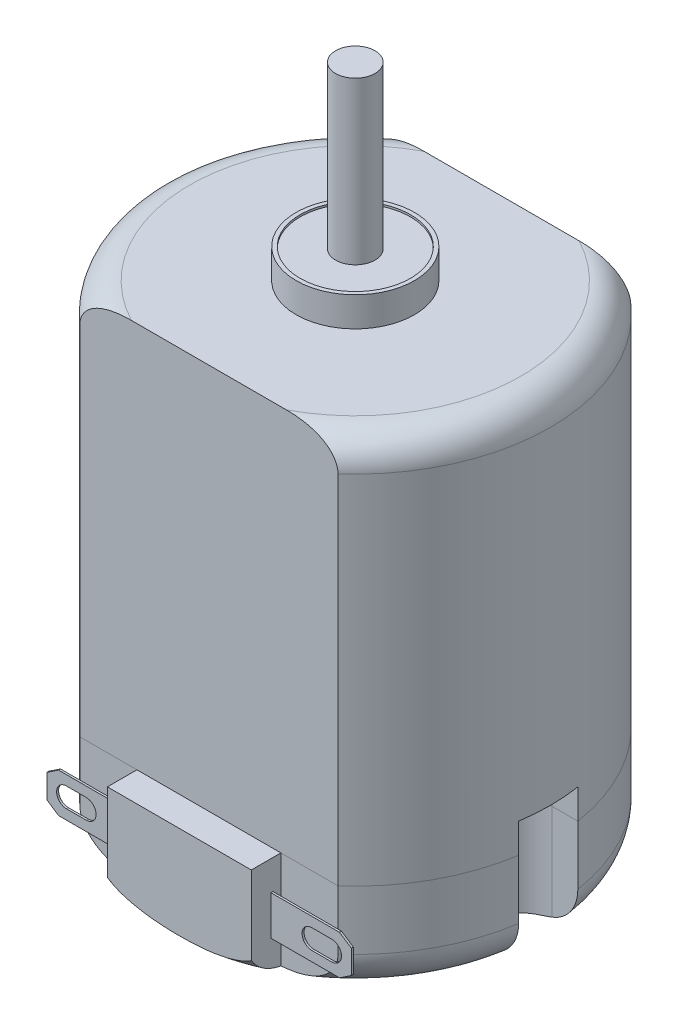
SolidWorks part; units mm, degrees
ref_plane "Front Plane" through (0, 0, 0) normal (0, 0, 1) x (1, 0, 0)
ref_plane "Top Plane" through (0, 0, 0) normal (0, 1, 0) x (1, 0, 0)
ref_plane "Right Plane" through (0, 0, 0) normal (1, 0, 0) x (0, 0, -1)
sketch "Sketch1" plane through (0, 0, 0) normal (0, 1, 0) x (1, 0, 0)
  line L0 (-6.5482, 7.425) -> (6.5482, 7.425)
  line L2 (6.5482, -7.425) -> (-6.5482, -7.425)
  arc A0 (-6.5482, 7.425) -> (-6.5482, -7.425) centre (0, 0) ccw
  arc A1 (6.5482, -7.425) -> (6.5482, 7.425) centre (0, 0) ccw
  point P1 (0, 0)
  point P4 (-6.5482, -7.425)
  dimension "D1" = 19.8
  dimension "D2" = 14.85
extrude "Boss-Extrude1" add sketch "Sketch1" along normal blind 19.6
sketch "Sketch2" plane through (0, 0, 0) normal (0, -1, 0) x (1, 0, 0)
  line L0 (6.5482, -7.425) -> (-6.5482, -7.425) construction
  line L1 (-6.5482, -7.425) -> (6.5482, -7.425)
  line L2 (-6.5482, 7.425) -> (-3.65, 7.425)
  line L3 (-6.5482, 7.425) -> (6.5482, 7.425) construction
  line L4 (-3.65, 7.425) -> (-3.65, 8.925)
  line L5 (-3.65, 8.925) -> (3.65, 8.925)
  line L6 (3.65, 8.925) -> (3.65, 7.425)
  line L7 (3.65, 7.425) -> (6.5482, 7.425)
  arc A0 (6.5482, 7.425) -> (6.5482, -7.425) centre (0, 0) cw
  arc A1 (-6.5482, 7.425) -> (-6.5482, -7.425) centre (0, 0) ccw
  arc A2 (-6.5482, 7.425) -> (-6.5482, -7.425) centre (0, 0) ccw construction
  dimension "D1" = 7.3
  dimension "D2" = 1.5
extrude "Boss-Extrude2" add sketch "Sketch2" along normal blind 5 separate body
sketch "Sketch3" plane through (0, -5, 0) normal (0, -1, 0) x (1, 0, 0)
  line L0 (-2.8652, -3.975) -> (2.8652, -3.975)
  line L1 (-6.5482, -7.425) -> (6.5482, -7.425) construction
  line L2 (0, 0) -> (0, 2.5) construction
  line L3 (-2.75, 3.4) -> (2.75, 3.4)
  line L4 (-2.75, 3.4) -> (-2.75, 2.5)
  line L5 (-2.75, 2.5) -> (2.75, 2.5)
  line L6 (2.75, 3.4) -> (2.75, 2.5)
  arc A0 (2.8652, -3.975) -> (-2.8652, -3.975) centre (0, 0) ccw
  dimension "D1" = 9.8
  dimension "D2" = 3.45
  dimension "D3" = 5.5
  dimension "D4" = 0.9
  dimension "D5" = 2.5
extrude "Boss-Extrude3" add sketch "Sketch3" along normal blind 2.3
sketch "Sketch4" plane through (0, -7.3, 0) normal (0, -1, 0) x (1, 0, 0)
  circle A0 centre (0, 0) radius 1
  dimension "D1" = 2
extrude "Boss-Extrude4" add sketch "Sketch4" along normal blind 0.5
sketch "Sketch5" plane through (0, -5, 0) normal (0, -1, 0) x (1, 0, 0)
  line L0 (-8.475, 0) -> (0, 0) construction
  line L1 (0, 0) -> (8.475, 0) construction
  line L2 (-8.475, 1.5) -> (-9.7857, 1.5)
  line L3 (8.475, 1.5) -> (9.7857, 1.5)
  line L4 (-8.475, -1.5) -> (-9.7857, -1.5)
  line L6 (8.475, -1.5) -> (9.7857, -1.5)
  arc A0 (-8.475, -1.5) -> (-8.475, 1.5) centre (-8.475, 0) ccw
  arc A1 (8.475, 1.5) -> (8.475, -1.5) centre (8.475, 0) ccw
  arc A2 (-6.5482, 7.425) -> (-6.5482, -7.425) centre (0, 0) ccw construction
  arc A3 (6.5482, -7.425) -> (6.5482, 7.425) centre (0, 0) ccw construction
  arc A4 (-9.7857, 1.5) -> (-9.7857, -1.5) centre (0, 0) ccw
  arc A5 (9.7857, -1.5) -> (9.7857, 1.5) centre (0, 0) ccw
  arc M1 (6.5482, -7.425) -> (6.5482, 7.425) centre (0, 0) ccw
  arc M7 (-6.5482, 7.425) -> (-6.5482, -7.425) centre (0, 0) ccw
  dimension "D1" = 16.95
  dimension "D2" = 1.5
extrude "Cut-Extrude1" cut sketch "Sketch5" against normal blind 6.5 contours L4 A0 L2 M7 | L3 A1 L6 M1 region at (-8.5578, -5, 0) region at (8.5578, -5, 0)
fillet "Fillet1" radius 2 3 edges at (8.6877, -5, -4.747) (-8.6877, -5, 4.747) (-8.6877, -5, -4.747)
sketch "Sketch7" plane through (0, 0, 0) normal (1, 0, 0) x (0, 0, -1)
  line L0 (-8.925, -3.9816) -> (-8.925, 0) construction
  line L1 (-7.925, -3.5) -> (-7.825, -3.5)
  line L2 (-7.925, -3.5) -> (-7.925, -1.5)
  line L3 (-7.925, -1.5) -> (-7.825, -1.5)
  line L4 (-7.825, -3.5) -> (-7.825, -1.5)
  line L5 (-4.6164, -5) -> (-14.6472, -5) construction
  line L6 (-7.9, -5) -> (-1.3328, -5) construction
  line L7 (-7.875, -3.5) -> (-7.875, -5) construction
  line L10 (-7.875, -1.5) -> (-7.875, 0) construction
  line L11 (-8.925, 0) -> (-7.425, 0) construction
  dimension "D1" = 2
  dimension "D2" = 0.1
  dimension "D3" = 1
extrude "Boss-Extrude5" add sketch "Sketch7" along normal blind 7.725 and the other way blind 7.725
sketch "Sketch8" plane through (0, 0, 7.925) normal (0, 0, 1) x (1, 0, 0)
  line L0 (6.725, -2.5) -> (5.725, -2.5) construction
  line L1 (6.725, -3) -> (5.725, -3)
  line L2 (6.725, -2) -> (5.725, -2)
  line L3 (0, 0) -> (0, -3.2841) construction
  line L4 (6.225, -2.5) -> (3.65, -2.5) construction
  line L5 (3.65, -3.5) -> (3.65, -1.5) construction
  line L6 (3.65, -3.5) -> (7.725, -3.5) construction
  line L7 (7.725, -1.5) -> (7.725, -3.5) construction
  line L8 (7.725, -1.9) -> (7.125, -1.5)
  line L9 (3.65, -1.5) -> (7.725, -1.5) construction
  line L10 (7.125, -1.5) -> (7.725, -1.5)
  line L11 (7.725, -1.5) -> (7.725, -1.9)
  line L12 (7.725, -3.5) -> (7.725, -3.1)
  line L13 (7.125, -3.5) -> (7.725, -3.5)
  line L14 (7.725, -3.1) -> (7.125, -3.5)
  line L15 (-6.725, -2.5) -> (-5.725, -2.5) construction
  line L16 (-6.725, -3) -> (-5.725, -3)
  line L17 (-6.725, -2) -> (-5.725, -2)
  line L18 (-7.725, -3.1) -> (-7.125, -3.5)
  line L19 (-7.125, -3.5) -> (-7.725, -3.5)
  line L20 (-7.725, -3.5) -> (-7.725, -3.1)
  line L21 (-7.725, -1.5) -> (-7.725, -1.9)
  line L22 (-7.125, -1.5) -> (-7.725, -1.5)
  line L23 (-7.725, -1.9) -> (-7.125, -1.5)
  arc A0 (6.725, -3) -> (6.725, -2) centre (6.725, -2.5) ccw
  arc A1 (5.725, -2) -> (5.725, -3) centre (5.725, -2.5) ccw
  arc A2 (-6.725, -3) -> (-6.725, -2) centre (-6.725, -2.5) cw
  arc A3 (-5.725, -2) -> (-5.725, -3) centre (-5.725, -2.5) cw
  point P2 (6.225, -2.5)
  point P27 (-6.225, -2.5)
  dimension "D2" = 1
  dimension "D3" = 1
  dimension "D1" = 0.5
  dimension "D4" = 0.4
  dimension "D5" = 0.6
extrude "Cut-Extrude2" cut sketch "Sketch8" against normal blind 0.1
sketch "Sketch9" plane through (0, 19.6, 0) normal (0, 1, 0) x (1, 0, 0)
  circle A0 centre (0, 0) radius 3
  dimension "D1" = 6
extrude "Boss-Extrude6" add sketch "Sketch9" along normal blind 1.5
sketch "Sketch10" plane through (0, 21.1, 0) normal (0, 1, 0) x (1, 0, 0)
  circle A0 centre (0, 0) radius 2.8
  circle A1 centre (0, 0) radius 3 construction
  dimension "D1" = 0.2
extrude "Cut-Extrude3" cut sketch "Sketch10" against normal blind 0.1
sketch "Sketch11" plane through (0, 21, 0) normal (0, 1, 0) x (1, 0, 0)
  circle A0 centre (0, 0) radius 1
  dimension "D1" = 2
extrude "Boss-Extrude7" add sketch "Sketch11" along normal blind 8.2
fillet "Fillet2" radius 1.5 2 edges at (9.9, 19.6, 0) (-9.9, 19.6, 0)
